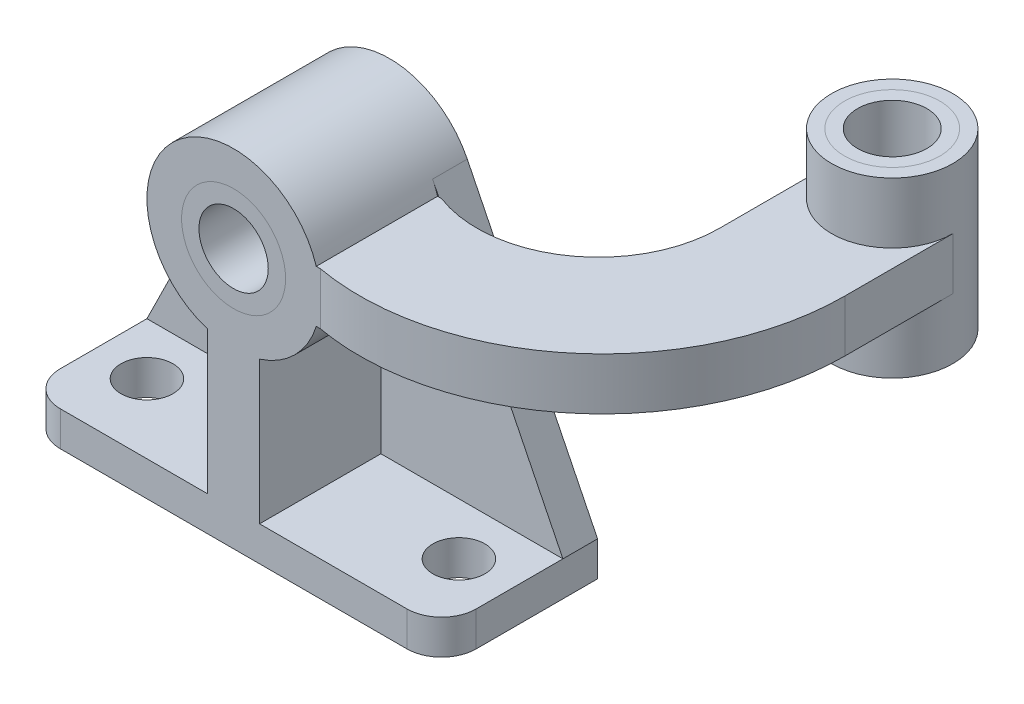
SolidWorks part; units mm, degrees
ref_plane "Front Plane" through (0, 0, 0) normal (0, 0, 1) x (1, 0, 0)
ref_plane "Top Plane" through (0, 0, 0) normal (0, 1, 0) x (1, 0, 0)
ref_plane "Right Plane" through (0, 0, 0) normal (1, 0, 0) x (0, 0, -1)
sketch "Sketch1" plane through (0, 0, 0) normal (0, 0, 1) x (1, 0, 0)
  line L0 (0, 8.2577) -> (0, -20.0305) construction
  line L1 (-12, -15) -> (12, -15)
  line L2 (12, -15) -> (12, -13)
  line L3 (12, -13) -> (-12, -13)
  line L4 (-12, -13) -> (-12, -15)
  line L5 (-12, -13) -> (-4.4827, 2.2148)
  line L6 (12, -13) -> (4.4827, 2.2148)
  line L7 (1.5, -4.7697) -> (1.5, -13)
  line L8 (-1.5, -4.7697) -> (-1.5, -13)
  circle A0 centre (0, 0) radius 3
  circle A1 centre (0, 0) radius 2
  circle A2 centre (0, 0) radius 5
  point P5 (0, -15)
  dimension "D3" = 4
  dimension "D4" = 6
  dimension "D5" = 10
  dimension "D1" = 2
  dimension "D2" = 24
  dimension "D6" = 15
  dimension "D7" = 3
extrude "Boss-Extrude1" add sketch "Sketch1" along normal blind 2 contours A2 L7 L3 L6 | A2 L5 L3 L8 region at (-5.7372, -8.23, 0) region at (5.7372, -8.23, 0)
extrude "Boss-Extrude2" add sketch "Sketch1<3>" along normal blind 9 contours L3 L0 L1 L2 | L0 L3 L4 L1 | A2 L0 A0 | L0 A2 A0 | A2 L0 L3 L7 | L0 A2 L8 L3 region at (2.5797, 4.152, 0) region at (-0.1118, 4, 0) region at (6, -14, 0) region at (-6, -14, 0) region at (-0.7535, -8.9617, 0) region at (0.7535, -8.9617, 0)
sketch "Sketch1<3>" plane through (0, 0, 0) normal (0, 0, 1) x (1, 0, 0) same geometry as "Sketch1"
extrude "Boss-Extrude3" add sketch "Sketch1<4>" along normal blind 9 separate body contours L0 A0 A1 | A0 L0 A1 region at (2.0739, 2.0739, 0) region at (-0.0671, 2.5, 0)
sketch "Sketch1<4>" plane through (0, 0, 0) normal (0, 0, 1) x (1, 0, 0) same geometry as "Sketch1"
sketch "Sketch2" plane through (0, -13, 0) normal (0, 1, 0) x (1, 0, 0)
  line L0 (-1.5, -9) -> (-12, -9) construction
  circle A0 centre (9, -5) radius 1.5
  circle A1 centre (-9, -5) radius 1.5
  dimension "D1" = 3
  dimension "D2" = 4
  dimension "D3" = 9
  dimension "D4" = 9
extrude "Cut-Extrude1" cut sketch "Sketch2" against normal up to next (2 mm away)
sketch "Sketch4" plane through (0, 0, 0) normal (0, 1, 0) x (1, 0, 0)
  line L0 (14.5, 11) -> (14.5, 4.5383)
  line L1 (21.5, 11) -> (21.5, 4.775)
  line L2 (5, -2) -> (5, -9)
  line L3 (5, -2) -> (3.7379, -2)
  line L4 (3.7379, -2) -> (3.7379, -9)
  line L5 (3.7379, -9) -> (5, -9)
  line L6 (3.7379, -9) -> (5, -9)
  circle A0 centre (18, 11) radius 2.75
  circle A1 centre (18, 11) radius 3.5
  circle A2 centre (18, 11) radius 2
  arc A3 (14.5, 4.5383) -> (5, -2) centre (7.5, 4.5383) cw
  arc A4 (21.5, 4.775) -> (5, -9) centre (7.5, 4.775) cw
  dimension "D1" = 4
  dimension "D2" = 5.5
  dimension "D3" = 7
  dimension "D5" = 18
  dimension "D6" = 7
  dimension "D7" = 14
  dimension "D4" = 11
extrude "Boss-Extrude4" add sketch "Sketch4" along normal mid plane 3 contours A4 L1 A1 L0 A3 L2 | L4 L5 L2 L3 region at (14.1258, 0, 1.1918) region at (4.369, 0, 5.5)
extrude "Boss-Extrude5" add sketch "Sketch4<4>" along normal mid plane 10 contours A1 A0 region at (18, 0, -14.401)
sketch "Sketch4<4>" plane through (0, 0, 0) normal (0, 1, 0) x (1, 0, 0) same geometry as "Sketch4"
extrude "Boss-Extrude6" add sketch "Sketch4<5>" along normal mid plane 10 separate body contours A0 A2 region at (15.3278, 0, -11)
sketch "Sketch4<5>" plane through (0, 0, 0) normal (0, 1, 0) x (1, 0, 0) same geometry as "Sketch4"
fillet "Fillet1" radius 2 2 edges at (-12, -14, 9) (12, -14, 9)
